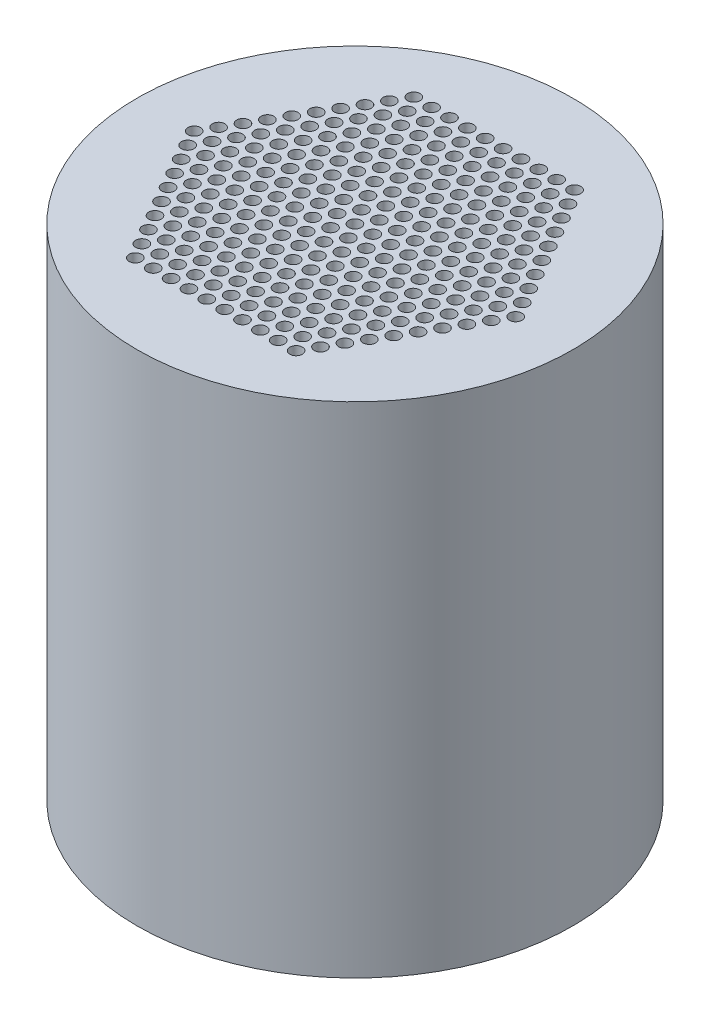
SolidWorks part; units mm, degrees
material "Água"
ref_plane "Plano frontal" through (0, 0, 0) normal (0, 0, 1) x (1, 0, 0)
ref_plane "Plano superior" through (0, 0, 0) normal (0, 1, 0) x (1, 0, 0)
ref_plane "Plano direito" through (0, 0, 0) normal (1, 0, 0) x (0, 0, -1)
sketch "Esboço1" plane through (0, 0, 0) normal (0, 1, 0) x (1, 0, 0)
  circle A0 centre (0, 0) radius 610
  dimension "D1" = 1220
extrude "agua" add sketch "Esboço1" along normal blind 1397
sketch "Esboço2" plane through (0, 1397, 0) normal (0, 1, 0) x (1, 0, 0)
  line L0 (0, -642.4629) -> (0, 642.4629) construction
  line L1 (-237.9367, 0) -> (243.6239, 0) construction
  circle A1 centre (0, 0) radius 17.5
  circle A2 centre (0, 0) radius 25 construction
  circle A26 centre (-25, 43.3013) radius 17.5
  circle A29 centre (-25, 43.3013) radius 25 construction
  circle A53 centre (0, 86.6025) radius 17.5
  circle A56 centre (0, 86.6025) radius 25 construction
  circle A62 centre (-25, 129.9038) radius 17.5
  circle A65 centre (-25, 129.9038) radius 25 construction
  circle A71 centre (25, 129.9038) radius 17.5
  circle A74 centre (25, 129.9038) radius 25 construction
  circle A80 centre (0, 173.2051) radius 17.5
  circle A83 centre (0, 173.2051) radius 25 construction
  circle A88 centre (25, 43.3013) radius 17.5
  circle A89 centre (25, 43.3013) radius 25 construction
  circle A93 centre (-25, 216.5064) radius 17.5
  circle A94 centre (-25, 216.5064) radius 25 construction
  circle A96 centre (25, 216.5064) radius 17.5
  circle A97 centre (25, 216.5064) radius 25 construction
  circle A99 centre (0, 259.8076) radius 17.5
  circle A100 centre (0, 259.8076) radius 25 construction
  circle A102 centre (-25, 303.1089) radius 17.5
  circle A103 centre (-25, 303.1089) radius 25 construction
  circle A105 centre (25, 303.1089) radius 17.5
  circle A106 centre (25, 303.1089) radius 25 construction
  circle A108 centre (0, 346.4102) radius 17.5
  circle A109 centre (0, 346.4102) radius 25 construction
  circle A111 centre (-25, 389.7114) radius 17.5
  circle A112 centre (-25, 389.7114) radius 25 construction
  circle A114 centre (25, 389.7114) radius 17.5
  circle A115 centre (25, 389.7114) radius 25 construction
  circle A331 centre (50, 0) radius 17.5
  circle A332 centre (50, 0) radius 25 construction
  circle A333 centre (100, 0) radius 17.5
  circle A334 centre (100, 0) radius 25 construction
  circle A335 centre (150, 0) radius 17.5
  circle A336 centre (150, 0) radius 25 construction
  circle A337 centre (200, 0) radius 17.5
  circle A338 centre (200, 0) radius 25 construction
  circle A339 centre (250, 0) radius 17.5
  circle A340 centre (250, 0) radius 25 construction
  circle A341 centre (300, 0) radius 17.5
  circle A342 centre (300, 0) radius 25 construction
  circle A343 centre (350, 0) radius 17.5
  circle A344 centre (350, 0) radius 25 construction
  circle A345 centre (400, 0) radius 17.5
  circle A346 centre (400, 0) radius 25 construction
  circle A347 centre (450, 0) radius 17.5
  circle A348 centre (450, 0) radius 25 construction
  circle A349 centre (75, 43.3013) radius 17.5
  circle A350 centre (75, 43.3013) radius 25 construction
  circle A351 centre (50, 86.6025) radius 17.5
  circle A352 centre (50, 86.6025) radius 25 construction
  circle A353 centre (125, 43.3013) radius 17.5
  circle A354 centre (125, 43.3013) radius 25 construction
  circle A355 centre (100, 86.6025) radius 17.5
  circle A356 centre (100, 86.6025) radius 25 construction
  circle A357 centre (175, 43.3013) radius 17.5
  circle A358 centre (175, 43.3013) radius 25 construction
  circle A359 centre (150, 86.6025) radius 17.5
  circle A360 centre (150, 86.6025) radius 25 construction
  circle A361 centre (225, 43.3013) radius 17.5
  circle A362 centre (225, 43.3013) radius 25 construction
  circle A363 centre (200, 86.6025) radius 17.5
  circle A364 centre (200, 86.6025) radius 25 construction
  circle A365 centre (275, 43.3013) radius 17.5
  circle A366 centre (275, 43.3013) radius 25 construction
  circle A367 centre (250, 86.6025) radius 17.5
  circle A368 centre (250, 86.6025) radius 25 construction
  circle A369 centre (325, 43.3013) radius 17.5
  circle A370 centre (325, 43.3013) radius 25 construction
  circle A371 centre (300, 86.6025) radius 17.5
  circle A372 centre (300, 86.6025) radius 25 construction
  circle A373 centre (375, 43.3013) radius 17.5
  circle A374 centre (375, 43.3013) radius 25 construction
  circle A375 centre (350, 86.6025) radius 17.5
  circle A376 centre (350, 86.6025) radius 25 construction
  circle A377 centre (425, 43.3013) radius 17.5
  circle A378 centre (425, 43.3013) radius 25 construction
  circle A379 centre (400, 86.6025) radius 17.5
  circle A380 centre (400, 86.6025) radius 25 construction
  circle A381 centre (75, 129.9038) radius 17.5
  circle A382 centre (75, 129.9038) radius 25 construction
  circle A383 centre (50, 173.2051) radius 25 construction
  circle A384 centre (50, 173.2051) radius 17.5
  circle A385 centre (125, 129.9038) radius 17.5
  circle A386 centre (125, 129.9038) radius 25 construction
  circle A387 centre (100, 173.2051) radius 25 construction
  circle A388 centre (100, 173.2051) radius 17.5
  circle A389 centre (175, 129.9038) radius 17.5
  circle A390 centre (175, 129.9038) radius 25 construction
  circle A391 centre (150, 173.2051) radius 25 construction
  circle A392 centre (150, 173.2051) radius 17.5
  circle A393 centre (225, 129.9038) radius 17.5
  circle A394 centre (225, 129.9038) radius 25 construction
  circle A395 centre (200, 173.2051) radius 25 construction
  circle A396 centre (200, 173.2051) radius 17.5
  circle A397 centre (275, 129.9038) radius 17.5
  circle A398 centre (275, 129.9038) radius 25 construction
  circle A399 centre (250, 173.2051) radius 25 construction
  circle A400 centre (250, 173.2051) radius 17.5
  circle A401 centre (325, 129.9038) radius 17.5
  circle A402 centre (325, 129.9038) radius 25 construction
  circle A403 centre (300, 173.2051) radius 25 construction
  circle A404 centre (300, 173.2051) radius 17.5
  circle A405 centre (375, 129.9038) radius 17.5
  circle A406 centre (375, 129.9038) radius 25 construction
  circle A407 centre (350, 173.2051) radius 25 construction
  circle A408 centre (350, 173.2051) radius 17.5
  circle A409 centre (75, 216.5064) radius 17.5
  circle A410 centre (75, 216.5064) radius 25 construction
  circle A411 centre (50, 259.8076) radius 25 construction
  circle A412 centre (50, 259.8076) radius 17.5
  circle A413 centre (125, 216.5064) radius 17.5
  circle A414 centre (125, 216.5064) radius 25 construction
  circle A415 centre (100, 259.8076) radius 25 construction
  circle A416 centre (100, 259.8076) radius 17.5
  circle A417 centre (175, 216.5064) radius 17.5
  circle A418 centre (175, 216.5064) radius 25 construction
  circle A419 centre (150, 259.8076) radius 25 construction
  circle A420 centre (150, 259.8076) radius 17.5
  circle A421 centre (225, 216.5064) radius 17.5
  circle A422 centre (225, 216.5064) radius 25 construction
  circle A423 centre (200, 259.8076) radius 25 construction
  circle A424 centre (200, 259.8076) radius 17.5
  circle A425 centre (275, 216.5064) radius 17.5
  circle A426 centre (275, 216.5064) radius 25 construction
  circle A427 centre (250, 259.8076) radius 25 construction
  circle A428 centre (250, 259.8076) radius 17.5
  circle A429 centre (325, 216.5064) radius 17.5
  circle A430 centre (325, 216.5064) radius 25 construction
  circle A431 centre (300, 259.8076) radius 25 construction
  circle A432 centre (300, 259.8076) radius 17.5
  circle A433 centre (75, 303.1089) radius 17.5
  circle A434 centre (75, 303.1089) radius 25 construction
  circle A435 centre (50, 346.4102) radius 17.5
  circle A436 centre (50, 346.4102) radius 25 construction
  circle A437 centre (125, 303.1089) radius 17.5
  circle A438 centre (125, 303.1089) radius 25 construction
  circle A439 centre (100, 346.4102) radius 17.5
  circle A440 centre (100, 346.4102) radius 25 construction
  circle A441 centre (175, 303.1089) radius 17.5
  circle A442 centre (175, 303.1089) radius 25 construction
  circle A443 centre (150, 346.4102) radius 17.5
  circle A444 centre (150, 346.4102) radius 25 construction
  circle A445 centre (225, 303.1089) radius 17.5
  circle A446 centre (225, 303.1089) radius 25 construction
  circle A447 centre (200, 346.4102) radius 17.5
  circle A448 centre (200, 346.4102) radius 25 construction
  circle A449 centre (275, 303.1089) radius 17.5
  circle A450 centre (275, 303.1089) radius 25 construction
  circle A451 centre (250, 346.4102) radius 17.5
  circle A452 centre (250, 346.4102) radius 25 construction
  circle A453 centre (75, 389.7114) radius 17.5
  circle A454 centre (75, 389.7114) radius 25 construction
  circle A455 centre (125, 389.7114) radius 17.5
  circle A456 centre (125, 389.7114) radius 25 construction
  circle A457 centre (175, 389.7114) radius 17.5
  circle A458 centre (175, 389.7114) radius 25 construction
  circle A459 centre (225, 389.7114) radius 17.5
  circle A460 centre (225, 389.7114) radius 25 construction
  circle A461 centre (-225, 389.7114) radius 25 construction
  circle A462 centre (-175, 389.7114) radius 25 construction
  circle A463 centre (-125, 389.7114) radius 25 construction
  circle A464 centre (-75, 389.7114) radius 25 construction
  circle A465 centre (-250, 346.4102) radius 25 construction
  circle A466 centre (-275, 303.1089) radius 25 construction
  circle A467 centre (-200, 346.4102) radius 25 construction
  circle A468 centre (-225, 303.1089) radius 25 construction
  circle A469 centre (-150, 346.4102) radius 25 construction
  circle A470 centre (-175, 303.1089) radius 25 construction
  circle A471 centre (-100, 346.4102) radius 25 construction
  circle A472 centre (-125, 303.1089) radius 25 construction
  circle A473 centre (-50, 346.4102) radius 25 construction
  circle A474 centre (-75, 303.1089) radius 25 construction
  circle A475 centre (-300, 259.8076) radius 25 construction
  circle A476 centre (-325, 216.5064) radius 25 construction
  circle A477 centre (-250, 259.8076) radius 25 construction
  circle A478 centre (-275, 216.5064) radius 25 construction
  circle A479 centre (-200, 259.8076) radius 25 construction
  circle A480 centre (-225, 216.5064) radius 25 construction
  circle A481 centre (-150, 259.8076) radius 25 construction
  circle A482 centre (-175, 216.5064) radius 25 construction
  circle A483 centre (-100, 259.8076) radius 25 construction
  circle A484 centre (-125, 216.5064) radius 25 construction
  circle A485 centre (-50, 259.8076) radius 25 construction
  circle A486 centre (-75, 216.5064) radius 25 construction
  circle A487 centre (-350, 173.2051) radius 25 construction
  circle A488 centre (-375, 129.9038) radius 25 construction
  circle A489 centre (-300, 173.2051) radius 25 construction
  circle A490 centre (-325, 129.9038) radius 25 construction
  circle A491 centre (-250, 173.2051) radius 25 construction
  circle A492 centre (-275, 129.9038) radius 25 construction
  circle A493 centre (-200, 173.2051) radius 25 construction
  circle A494 centre (-225, 129.9038) radius 25 construction
  circle A495 centre (-150, 173.2051) radius 25 construction
  circle A496 centre (-175, 129.9038) radius 25 construction
  circle A497 centre (-100, 173.2051) radius 25 construction
  circle A498 centre (-125, 129.9038) radius 25 construction
  circle A499 centre (-50, 173.2051) radius 25 construction
  circle A500 centre (-75, 129.9038) radius 25 construction
  circle A501 centre (-400, 86.6025) radius 25 construction
  circle A502 centre (-425, 43.3013) radius 25 construction
  circle A503 centre (-350, 86.6025) radius 25 construction
  circle A504 centre (-375, 43.3013) radius 25 construction
  circle A505 centre (-300, 86.6025) radius 25 construction
  circle A506 centre (-325, 43.3013) radius 25 construction
  circle A507 centre (-250, 86.6025) radius 25 construction
  circle A508 centre (-275, 43.3013) radius 25 construction
  circle A509 centre (-200, 86.6025) radius 25 construction
  circle A510 centre (-225, 43.3013) radius 25 construction
  circle A511 centre (-150, 86.6025) radius 25 construction
  circle A512 centre (-175, 43.3013) radius 25 construction
  circle A513 centre (-100, 86.6025) radius 25 construction
  circle A514 centre (-125, 43.3013) radius 25 construction
  circle A515 centre (-50, 86.6025) radius 25 construction
  circle A516 centre (-75, 43.3013) radius 25 construction
  circle A517 centre (-450, 0) radius 25 construction
  circle A518 centre (-400, 0) radius 25 construction
  circle A519 centre (-350, 0) radius 25 construction
  circle A520 centre (-300, 0) radius 25 construction
  circle A521 centre (-250, 0) radius 25 construction
  circle A522 centre (-200, 0) radius 25 construction
  circle A523 centre (-150, 0) radius 25 construction
  circle A524 centre (-100, 0) radius 25 construction
  circle A525 centre (-50, 0) radius 25 construction
  circle A526 centre (-225, 389.7114) radius 17.5
  circle A527 centre (-175, 389.7114) radius 17.5
  circle A528 centre (-125, 389.7114) radius 17.5
  circle A529 centre (-75, 389.7114) radius 17.5
  circle A530 centre (-250, 346.4102) radius 17.5
  circle A531 centre (-275, 303.1089) radius 17.5
  circle A532 centre (-200, 346.4102) radius 17.5
  circle A533 centre (-225, 303.1089) radius 17.5
  circle A534 centre (-150, 346.4102) radius 17.5
  circle A535 centre (-175, 303.1089) radius 17.5
  circle A536 centre (-100, 346.4102) radius 17.5
  circle A537 centre (-125, 303.1089) radius 17.5
  circle A538 centre (-50, 346.4102) radius 17.5
  circle A539 centre (-75, 303.1089) radius 17.5
  circle A540 centre (-300, 259.8076) radius 17.5
  circle A541 centre (-325, 216.5064) radius 17.5
  circle A542 centre (-250, 259.8076) radius 17.5
  circle A543 centre (-275, 216.5064) radius 17.5
  circle A544 centre (-200, 259.8076) radius 17.5
  circle A545 centre (-225, 216.5064) radius 17.5
  circle A546 centre (-150, 259.8076) radius 17.5
  circle A547 centre (-175, 216.5064) radius 17.5
  circle A548 centre (-100, 259.8076) radius 17.5
  circle A549 centre (-125, 216.5064) radius 17.5
  circle A550 centre (-50, 259.8076) radius 17.5
  circle A551 centre (-75, 216.5064) radius 17.5
  circle A552 centre (-350, 173.2051) radius 17.5
  circle A553 centre (-375, 129.9038) radius 17.5
  circle A554 centre (-300, 173.2051) radius 17.5
  circle A555 centre (-325, 129.9038) radius 17.5
  circle A556 centre (-250, 173.2051) radius 17.5
  circle A557 centre (-275, 129.9038) radius 17.5
  circle A558 centre (-200, 173.2051) radius 17.5
  circle A559 centre (-225, 129.9038) radius 17.5
  circle A560 centre (-150, 173.2051) radius 17.5
  circle A561 centre (-175, 129.9038) radius 17.5
  circle A562 centre (-100, 173.2051) radius 17.5
  circle A563 centre (-125, 129.9038) radius 17.5
  circle A564 centre (-50, 173.2051) radius 17.5
  circle A565 centre (-75, 129.9038) radius 17.5
  circle A566 centre (-400, 86.6025) radius 17.5
  circle A567 centre (-425, 43.3013) radius 17.5
  circle A568 centre (-350, 86.6025) radius 17.5
  circle A569 centre (-375, 43.3013) radius 17.5
  circle A570 centre (-300, 86.6025) radius 17.5
  circle A571 centre (-325, 43.3013) radius 17.5
  circle A572 centre (-250, 86.6025) radius 17.5
  circle A573 centre (-275, 43.3013) radius 17.5
  circle A574 centre (-200, 86.6025) radius 17.5
  circle A575 centre (-225, 43.3013) radius 17.5
  circle A576 centre (-150, 86.6025) radius 17.5
  circle A577 centre (-175, 43.3013) radius 17.5
  circle A578 centre (-100, 86.6025) radius 17.5
  circle A579 centre (-125, 43.3013) radius 17.5
  circle A580 centre (-50, 86.6025) radius 17.5
  circle A581 centre (-75, 43.3013) radius 17.5
  circle A582 centre (-450, 0) radius 17.5
  circle A583 centre (-400, 0) radius 17.5
  circle A584 centre (-350, 0) radius 17.5
  circle A585 centre (-300, 0) radius 17.5
  circle A586 centre (-250, 0) radius 17.5
  circle A587 centre (-200, 0) radius 17.5
  circle A588 centre (-150, 0) radius 17.5
  circle A589 centre (-100, 0) radius 17.5
  circle A590 centre (-50, 0) radius 17.5
  circle A591 centre (-75, -43.3013) radius 25 construction
  circle A592 centre (-50, -86.6025) radius 25 construction
  circle A593 centre (-125, -43.3013) radius 25 construction
  circle A594 centre (-100, -86.6025) radius 25 construction
  circle A595 centre (-175, -43.3013) radius 25 construction
  circle A596 centre (-150, -86.6025) radius 25 construction
  circle A597 centre (-225, -43.3013) radius 25 construction
  circle A598 centre (-200, -86.6025) radius 25 construction
  circle A599 centre (-275, -43.3013) radius 25 construction
  circle A600 centre (-250, -86.6025) radius 25 construction
  circle A601 centre (-325, -43.3013) radius 25 construction
  circle A602 centre (-300, -86.6025) radius 25 construction
  circle A603 centre (-375, -43.3013) radius 25 construction
  circle A604 centre (-350, -86.6025) radius 25 construction
  circle A605 centre (-425, -43.3013) radius 25 construction
  circle A606 centre (-400, -86.6025) radius 25 construction
  circle A607 centre (-75, -129.9038) radius 25 construction
  circle A608 centre (-50, -173.2051) radius 25 construction
  circle A609 centre (-125, -129.9038) radius 25 construction
  circle A610 centre (-100, -173.2051) radius 25 construction
  circle A611 centre (-175, -129.9038) radius 25 construction
  circle A612 centre (-150, -173.2051) radius 25 construction
  circle A613 centre (-225, -129.9038) radius 25 construction
  circle A614 centre (-200, -173.2051) radius 25 construction
  circle A615 centre (-275, -129.9038) radius 25 construction
  circle A616 centre (-250, -173.2051) radius 25 construction
  circle A617 centre (-325, -129.9038) radius 25 construction
  circle A618 centre (-300, -173.2051) radius 25 construction
  circle A619 centre (-375, -129.9038) radius 25 construction
  circle A620 centre (-350, -173.2051) radius 25 construction
  circle A621 centre (-75, -216.5064) radius 25 construction
  circle A622 centre (-50, -259.8076) radius 25 construction
  circle A623 centre (-125, -216.5064) radius 25 construction
  circle A624 centre (-100, -259.8076) radius 25 construction
  circle A625 centre (-175, -216.5064) radius 25 construction
  circle A626 centre (-150, -259.8076) radius 25 construction
  circle A627 centre (-225, -216.5064) radius 25 construction
  circle A628 centre (-200, -259.8076) radius 25 construction
  circle A629 centre (-275, -216.5064) radius 25 construction
  circle A630 centre (-250, -259.8076) radius 25 construction
  circle A631 centre (-325, -216.5064) radius 25 construction
  circle A632 centre (-300, -259.8076) radius 25 construction
  circle A633 centre (-75, -303.1089) radius 25 construction
  circle A634 centre (-50, -346.4102) radius 25 construction
  circle A635 centre (-125, -303.1089) radius 25 construction
  circle A636 centre (-100, -346.4102) radius 25 construction
  circle A637 centre (-175, -303.1089) radius 25 construction
  circle A638 centre (-150, -346.4102) radius 25 construction
  circle A639 centre (-225, -303.1089) radius 25 construction
  circle A640 centre (-200, -346.4102) radius 25 construction
  circle A641 centre (-275, -303.1089) radius 25 construction
  circle A642 centre (-250, -346.4102) radius 25 construction
  circle A643 centre (-75, -389.7114) radius 25 construction
  circle A644 centre (-125, -389.7114) radius 25 construction
  circle A645 centre (-175, -389.7114) radius 25 construction
  circle A646 centre (-225, -389.7114) radius 25 construction
  circle A647 centre (225, -389.7114) radius 25 construction
  circle A648 centre (175, -389.7114) radius 25 construction
  circle A649 centre (125, -389.7114) radius 25 construction
  circle A650 centre (75, -389.7114) radius 25 construction
  circle A651 centre (250, -346.4102) radius 25 construction
  circle A652 centre (275, -303.1089) radius 25 construction
  circle A653 centre (200, -346.4102) radius 25 construction
  circle A654 centre (225, -303.1089) radius 25 construction
  circle A655 centre (150, -346.4102) radius 25 construction
  circle A656 centre (175, -303.1089) radius 25 construction
  circle A657 centre (100, -346.4102) radius 25 construction
  circle A658 centre (125, -303.1089) radius 25 construction
  circle A659 centre (50, -346.4102) radius 25 construction
  circle A660 centre (75, -303.1089) radius 25 construction
  circle A661 centre (300, -259.8076) radius 25 construction
  circle A662 centre (325, -216.5064) radius 25 construction
  circle A663 centre (250, -259.8076) radius 25 construction
  circle A664 centre (275, -216.5064) radius 25 construction
  circle A665 centre (200, -259.8076) radius 25 construction
  circle A666 centre (225, -216.5064) radius 25 construction
  circle A667 centre (150, -259.8076) radius 25 construction
  circle A668 centre (175, -216.5064) radius 25 construction
  circle A669 centre (100, -259.8076) radius 25 construction
  circle A670 centre (125, -216.5064) radius 25 construction
  circle A671 centre (50, -259.8076) radius 25 construction
  circle A672 centre (75, -216.5064) radius 25 construction
  circle A673 centre (350, -173.2051) radius 25 construction
  circle A674 centre (375, -129.9038) radius 25 construction
  circle A675 centre (300, -173.2051) radius 25 construction
  circle A676 centre (325, -129.9038) radius 25 construction
  circle A677 centre (250, -173.2051) radius 25 construction
  circle A678 centre (275, -129.9038) radius 25 construction
  circle A679 centre (200, -173.2051) radius 25 construction
  circle A680 centre (225, -129.9038) radius 25 construction
  circle A681 centre (150, -173.2051) radius 25 construction
  circle A682 centre (175, -129.9038) radius 25 construction
  circle A683 centre (100, -173.2051) radius 25 construction
  circle A684 centre (125, -129.9038) radius 25 construction
  circle A685 centre (50, -173.2051) radius 25 construction
  circle A686 centre (75, -129.9038) radius 25 construction
  circle A687 centre (400, -86.6025) radius 25 construction
  circle A688 centre (425, -43.3013) radius 25 construction
  circle A689 centre (350, -86.6025) radius 25 construction
  circle A690 centre (375, -43.3013) radius 25 construction
  circle A691 centre (300, -86.6025) radius 25 construction
  circle A692 centre (325, -43.3013) radius 25 construction
  circle A693 centre (250, -86.6025) radius 25 construction
  circle A694 centre (275, -43.3013) radius 25 construction
  circle A695 centre (200, -86.6025) radius 25 construction
  circle A696 centre (225, -43.3013) radius 25 construction
  circle A697 centre (150, -86.6025) radius 25 construction
  circle A698 centre (175, -43.3013) radius 25 construction
  circle A699 centre (100, -86.6025) radius 25 construction
  circle A700 centre (125, -43.3013) radius 25 construction
  circle A701 centre (50, -86.6025) radius 25 construction
  circle A702 centre (75, -43.3013) radius 25 construction
  circle A703 centre (25, -389.7114) radius 25 construction
  circle A704 centre (-25, -389.7114) radius 25 construction
  circle A705 centre (0, -346.4102) radius 25 construction
  circle A706 centre (25, -303.1089) radius 25 construction
  circle A707 centre (-25, -303.1089) radius 25 construction
  circle A708 centre (0, -259.8076) radius 25 construction
  circle A709 centre (25, -216.5064) radius 25 construction
  circle A710 centre (-25, -216.5064) radius 25 construction
  circle A711 centre (25, -43.3013) radius 25 construction
  circle A712 centre (0, -173.2051) radius 25 construction
  circle A713 centre (25, -129.9038) radius 25 construction
  circle A714 centre (-25, -129.9038) radius 25 construction
  circle A715 centre (0, -86.6025) radius 25 construction
  circle A716 centre (-25, -43.3013) radius 25 construction
  circle A717 centre (-75, -43.3013) radius 17.5
  circle A718 centre (-50, -86.6025) radius 17.5
  circle A719 centre (-125, -43.3013) radius 17.5
  circle A720 centre (-100, -86.6025) radius 17.5
  circle A721 centre (-175, -43.3013) radius 17.5
  circle A722 centre (-150, -86.6025) radius 17.5
  circle A723 centre (-225, -43.3013) radius 17.5
  circle A724 centre (-200, -86.6025) radius 17.5
  circle A725 centre (-275, -43.3013) radius 17.5
  circle A726 centre (-250, -86.6025) radius 17.5
  circle A727 centre (-325, -43.3013) radius 17.5
  circle A728 centre (-300, -86.6025) radius 17.5
  circle A729 centre (-375, -43.3013) radius 17.5
  circle A730 centre (-350, -86.6025) radius 17.5
  circle A731 centre (-425, -43.3013) radius 17.5
  circle A732 centre (-400, -86.6025) radius 17.5
  circle A733 centre (-75, -129.9038) radius 17.5
  circle A734 centre (-50, -173.2051) radius 17.5
  circle A735 centre (-125, -129.9038) radius 17.5
  circle A736 centre (-100, -173.2051) radius 17.5
  circle A737 centre (-175, -129.9038) radius 17.5
  circle A738 centre (-150, -173.2051) radius 17.5
  circle A739 centre (-225, -129.9038) radius 17.5
  circle A740 centre (-200, -173.2051) radius 17.5
  circle A741 centre (-275, -129.9038) radius 17.5
  circle A742 centre (-250, -173.2051) radius 17.5
  circle A743 centre (-325, -129.9038) radius 17.5
  circle A744 centre (-300, -173.2051) radius 17.5
  circle A745 centre (-375, -129.9038) radius 17.5
  circle A746 centre (-350, -173.2051) radius 17.5
  circle A747 centre (-75, -216.5064) radius 17.5
  circle A748 centre (-50, -259.8076) radius 17.5
  circle A749 centre (-125, -216.5064) radius 17.5
  circle A750 centre (-100, -259.8076) radius 17.5
  circle A751 centre (-175, -216.5064) radius 17.5
  circle A752 centre (-150, -259.8076) radius 17.5
  circle A753 centre (-225, -216.5064) radius 17.5
  circle A754 centre (-200, -259.8076) radius 17.5
  circle A755 centre (-275, -216.5064) radius 17.5
  circle A756 centre (-250, -259.8076) radius 17.5
  circle A757 centre (-325, -216.5064) radius 17.5
  circle A758 centre (-300, -259.8076) radius 17.5
  circle A759 centre (-75, -303.1089) radius 17.5
  circle A760 centre (-50, -346.4102) radius 17.5
  circle A761 centre (-125, -303.1089) radius 17.5
  circle A762 centre (-100, -346.4102) radius 17.5
  circle A763 centre (-175, -303.1089) radius 17.5
  circle A764 centre (-150, -346.4102) radius 17.5
  circle A765 centre (-225, -303.1089) radius 17.5
  circle A766 centre (-200, -346.4102) radius 17.5
  circle A767 centre (-275, -303.1089) radius 17.5
  circle A768 centre (-250, -346.4102) radius 17.5
  circle A769 centre (-75, -389.7114) radius 17.5
  circle A770 centre (-125, -389.7114) radius 17.5
  circle A771 centre (-175, -389.7114) radius 17.5
  circle A772 centre (-225, -389.7114) radius 17.5
  circle A773 centre (225, -389.7114) radius 17.5
  circle A774 centre (175, -389.7114) radius 17.5
  circle A775 centre (125, -389.7114) radius 17.5
  circle A776 centre (75, -389.7114) radius 17.5
  circle A777 centre (250, -346.4102) radius 17.5
  circle A778 centre (275, -303.1089) radius 17.5
  circle A779 centre (200, -346.4102) radius 17.5
  circle A780 centre (225, -303.1089) radius 17.5
  circle A781 centre (150, -346.4102) radius 17.5
  circle A782 centre (175, -303.1089) radius 17.5
  circle A783 centre (100, -346.4102) radius 17.5
  circle A784 centre (125, -303.1089) radius 17.5
  circle A785 centre (50, -346.4102) radius 17.5
  circle A786 centre (75, -303.1089) radius 17.5
  circle A787 centre (300, -259.8076) radius 17.5
  circle A788 centre (325, -216.5064) radius 17.5
  circle A789 centre (250, -259.8076) radius 17.5
  circle A790 centre (275, -216.5064) radius 17.5
  circle A791 centre (200, -259.8076) radius 17.5
  circle A792 centre (225, -216.5064) radius 17.5
  circle A793 centre (150, -259.8076) radius 17.5
  circle A794 centre (175, -216.5064) radius 17.5
  circle A795 centre (100, -259.8076) radius 17.5
  circle A796 centre (125, -216.5064) radius 17.5
  circle A797 centre (50, -259.8076) radius 17.5
  circle A798 centre (75, -216.5064) radius 17.5
  circle A799 centre (350, -173.2051) radius 17.5
  circle A800 centre (375, -129.9038) radius 17.5
  circle A801 centre (300, -173.2051) radius 17.5
  circle A802 centre (325, -129.9038) radius 17.5
  circle A803 centre (250, -173.2051) radius 17.5
  circle A804 centre (275, -129.9038) radius 17.5
  circle A805 centre (200, -173.2051) radius 17.5
  circle A806 centre (225, -129.9038) radius 17.5
  circle A807 centre (150, -173.2051) radius 17.5
  circle A808 centre (175, -129.9038) radius 17.5
  circle A809 centre (100, -173.2051) radius 17.5
  circle A810 centre (125, -129.9038) radius 17.5
  circle A811 centre (50, -173.2051) radius 17.5
  circle A812 centre (75, -129.9038) radius 17.5
  circle A813 centre (400, -86.6025) radius 17.5
  circle A814 centre (425, -43.3013) radius 17.5
  circle A815 centre (350, -86.6025) radius 17.5
  circle A816 centre (375, -43.3013) radius 17.5
  circle A817 centre (300, -86.6025) radius 17.5
  circle A818 centre (325, -43.3013) radius 17.5
  circle A819 centre (250, -86.6025) radius 17.5
  circle A820 centre (275, -43.3013) radius 17.5
  circle A821 centre (200, -86.6025) radius 17.5
  circle A822 centre (225, -43.3013) radius 17.5
  circle A823 centre (150, -86.6025) radius 17.5
  circle A824 centre (175, -43.3013) radius 17.5
  circle A825 centre (100, -86.6025) radius 17.5
  circle A826 centre (125, -43.3013) radius 17.5
  circle A827 centre (50, -86.6025) radius 17.5
  circle A828 centre (75, -43.3013) radius 17.5
  circle A829 centre (25, -389.7114) radius 17.5
  circle A830 centre (-25, -389.7114) radius 17.5
  circle A831 centre (0, -346.4102) radius 17.5
  circle A832 centre (25, -303.1089) radius 17.5
  circle A833 centre (-25, -303.1089) radius 17.5
  circle A834 centre (0, -259.8076) radius 17.5
  circle A835 centre (25, -216.5064) radius 17.5
  circle A836 centre (-25, -216.5064) radius 17.5
  circle A837 centre (25, -43.3013) radius 17.5
  circle A838 centre (0, -173.2051) radius 17.5
  circle A839 centre (25, -129.9038) radius 17.5
  circle A840 centre (-25, -129.9038) radius 17.5
  circle A841 centre (0, -86.6025) radius 17.5
  circle A842 centre (-25, -43.3013) radius 17.5
  point P11 (0, 0)
  dimension "D1" = 50
  dimension "D2" = 35
  dimension "D3" = 50
  dimension "D4" = 9
  dimension "D5" = 50
  dimension "D6" = 50
  dimension "D7" = 50
  dimension "D8" = 50
  dimension "D9" = 50
extrude "vacuo" cut sketch "Esboço2" against normal blind 1231.9
